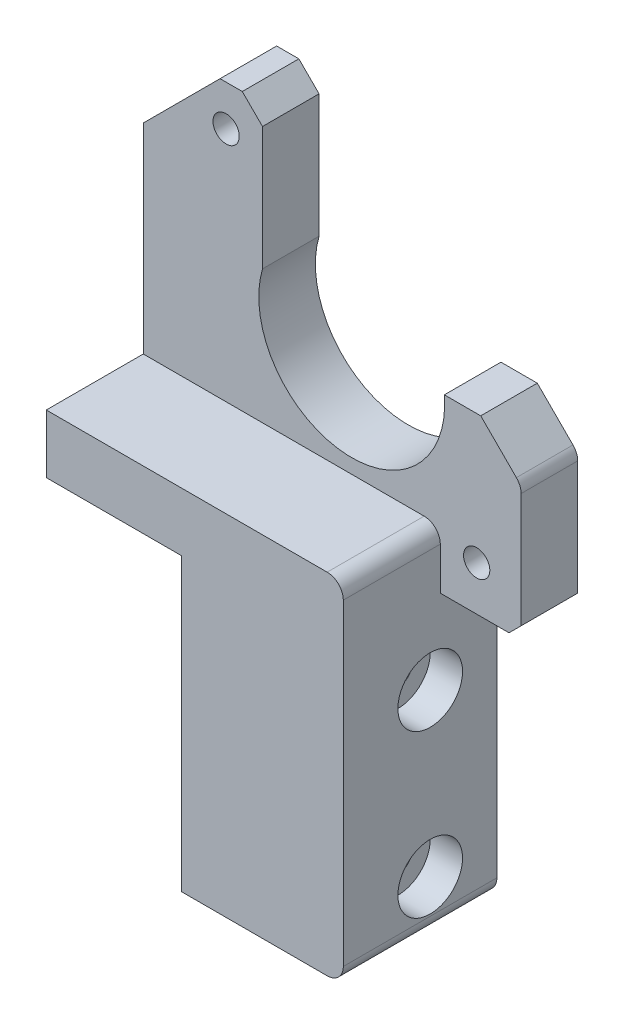
SolidWorks part; units mm, degrees
ref_plane "Front Plane" through (0, 0, 0) normal (0, 0, 1) x (1, 0, 0)
ref_plane "Top Plane" through (0, 0, 0) normal (0, 1, 0) x (1, 0, 0)
ref_plane "Right Plane" through (0, 0, 0) normal (1, 0, 0) x (0, 0, -1)
sketch "Sketch1" plane through (0, 0, 0) normal (0, 0, 1) x (1, 0, 0)
  line L0 (0, 0) -> (20, 0)
  line L1 (20, 0) -> (20, 43.25)
  line L2 (20, 43.25) -> (-16.75, 43.25)
  line L3 (-16.75, 43.25) -> (-16.75, 36)
  line L4 (-16.75, 36) -> (0, 36)
  line L5 (0, 36) -> (0, 0)
  dimension "D1" = 20
  dimension "D2" = 43.25
  dimension "D3" = 16.75
  dimension "D4" = 36
extrude "Boss-Extrude1" add sketch "Sketch1" along normal blind 19
sketch "Sketch2" plane through (0, 0, 0) normal (0, 0, -1) x (-1, 0, 0)
  line L0 (-20, 36) -> (16.75, 36)
  line L1 (16.75, 36) -> (16.75, 68)
  line L2 (16.75, 68) -> (7.25, 77.5)
  line L3 (7.25, 77.5) -> (4.5, 77.5)
  line L4 (4.5, 77.5) -> (2, 75)
  line L5 (2, 75) -> (2, 59.75)
  line L7 (-20, 0) -> (-20, 43.25) construction
  line L8 (-20, 36) -> (-28.5, 36)
  line L9 (-28.5, 36) -> (-30, 37.5)
  line L10 (-30, 37.5) -> (-30, 52.5)
  line L11 (-30, 52.5) -> (-25, 57.5)
  line L12 (-25, 57.5) -> (-20.5, 57.5)
  arc A0 (-20.5, 57.5) -> (2, 59.75) centre (-9.0408, 56.5326) ccw
  dimension "D16" = 23
  dimension "D1" = 45
  dimension "D2" = 32
  dimension "D3" = 9.5
  dimension "D4" = 2.75
  dimension "D5" = 45
  dimension "D6" = 2.5
  dimension "D7" = 15.25
  dimension "D9" = 8.5
  dimension "D10" = 135
  dimension "D11" = 1.5
  dimension "D12" = 15
  dimension "D13" = 45
  dimension "D14" = 5
  dimension "D15" = 4.5
extrude "Boss-Extrude2" add sketch "Sketch2" against normal blind 7
sketch "Sketch3" plane through (20, 0, 0) normal (1, 0, 0) x (0, 0, -1)
  line L0 (0, 0) -> (0, 36) construction
  line L1 (-8.25, 26.25) -> (-8.25, 6.25) construction
  line L2 (-19, 0) -> (0, 0) construction
  circle A0 centre (-8.25, 26.25) radius 1.75
  circle A1 centre (-8.25, 6.25) radius 1.75
  dimension "D4" = 3.5
  dimension "D1" = 8.25
  dimension "D2" = 26.25
  dimension "D3" = 6.25
extrude "Cut-Extrude1" cut sketch "Sketch3" against normal through all
sketch "Sketch6" plane through (20, 0, 0) normal (1, 0, 0) x (0, 0, -1)
  circle A0 centre (-8.25, 26.25) radius 4
  circle A1 centre (-8.25, 6.25) radius 4
  dimension "D1" = 8
extrude "Cut-Extrude4" cut sketch "Sketch6" against normal blind 4
sketch "Sketch7" plane through (0, 0, 0) normal (0, 0, -1) x (-1, 0, 0)
  line L0 (-28.5, 36) -> (-20, 36) construction
  line L1 (-30, 52.5) -> (-30, 37.5) construction
  line L2 (16.75, 36) -> (0, 36) construction
  circle A0 centre (6.5, 72.5) radius 1.625
  circle A1 centre (-24.5, 41.5) radius 1.625
  dimension "D1" = 3.25
  dimension "D2" = 3.25
  dimension "D3" = 5.5
  dimension "D4" = 5.5
  dimension "D5" = 36.5
  dimension "D6" = 36.5
extrude "Cut-Extrude5" cut sketch "Sketch7" against normal through all
fillet "Fillet1" radius 2 3 edges at (20, 43.25, 13) (30, 52.5, 3.5) (20, 0, 9.5)
